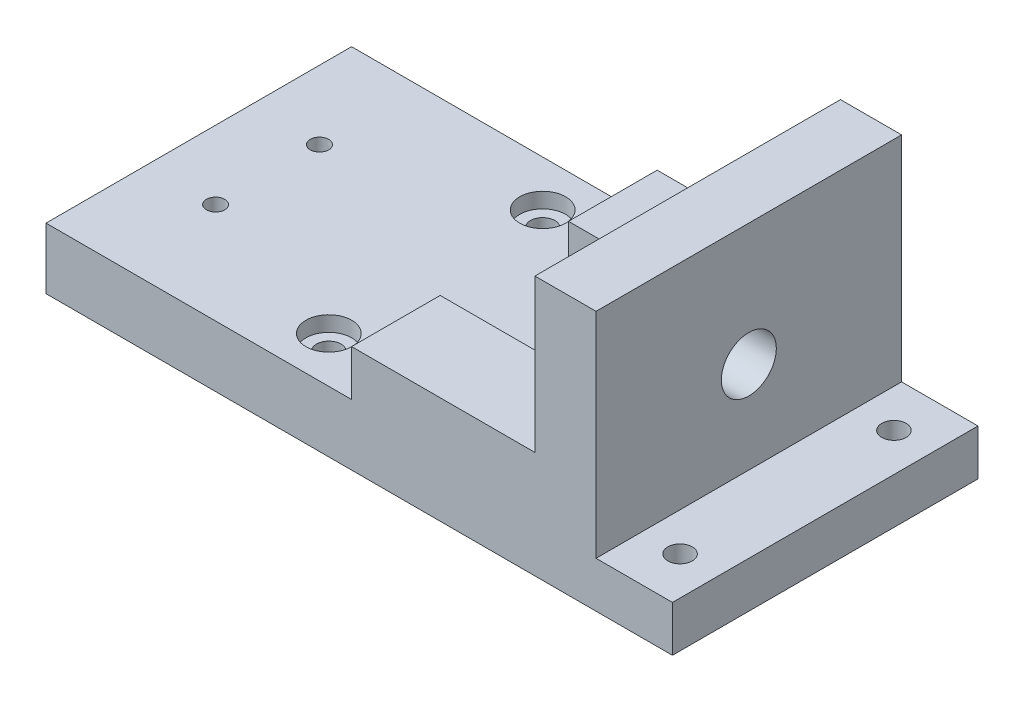
SolidWorks part; units mm, degrees
ref_plane "Front Plane" through (0, 0, 0) normal (0, 0, 1) x (1, 0, 0)
ref_plane "Top Plane" through (0, 0, 0) normal (0, 1, 0) x (1, 0, 0)
ref_plane "Right Plane" through (0, 0, 0) normal (1, 0, 0) x (0, 0, -1)
sketch "Sketch1" plane through (0, 0, 0) normal (0, 0, 1) x (1, 0, 0)
  line L0 (-307.2696, -26.3557) -> (-102.2696, -26.3557)
  line L1 (-102.2696, -26.3557) -> (-102.2696, -11.3557)
  line L5 (-147.2696, 58.6443) -> (-147.2696, 8.6443)
  line L7 (-307.2696, -6.3557) -> (-307.2696, -26.3557)
  line L8 (-307.2696, -6.3557) -> (-207.2696, -6.3557)
  line L9 (-207.2696, -6.3557) -> (-207.2696, 8.6443)
  line L10 (-207.2696, 8.6443) -> (-147.2696, 8.6443)
  line L11 (-147.2696, 58.6443) -> (-127.2696, 58.6443)
  line L12 (-127.2696, 58.6443) -> (-127.2696, -11.3557)
  line L13 (-127.2696, -11.3557) -> (-102.2696, -11.3557)
  dimension "D1" = 20
  dimension "D2" = 205
  dimension "D3" = 15
  dimension "D4" = 70
  dimension "D5" = 60
  dimension "D6" = 15
  dimension "D7" = 25
  dimension "D8" = 20
extrude "Boss-Extrude1" add sketch "Sketch1" along normal blind 100
sketch "Sketch2" plane through (0, 8.6443, 0) normal (0, 1, 0) x (1, 0, 0)
  line L0 (-207.2696, -29) -> (-147.2696, -29)
  line L1 (-207.2696, -100) -> (-207.2696, 0) construction
  line L2 (-147.2696, -100) -> (-147.2696, 0) construction
  line L3 (-207.2696, -29) -> (-207.2696, -71)
  line L4 (-207.2696, -71) -> (-147.2696, -71)
  line L5 (-147.2696, -100) -> (-147.2696, 0) construction
  line L6 (-147.2696, -71) -> (-147.2696, -29)
  line L9 (-207.2696, -100) -> (-207.2696, 0) construction
  point P14 (-207.2696, -50)
  dimension "D1" = 42
extrude "Cut-Extrude1" cut sketch "Sketch2" against normal blind 15
sketch "Sketch3" plane through (0, -6.3557, 0) normal (0, 1, 0) x (1, 0, 0)
  line L1 (-307.2696, -100) -> (-307.2696, 0) construction
  line L2 (-207.2696, 0) -> (-307.2696, 0) construction
  line L3 (-102.2696, -100) -> (-102.2696, 0) construction
  line L4 (-102.2696, 0) -> (-127.2696, 0) construction
  circle A0 centre (-284.7696, -33) radius 3
  circle A1 centre (-114.7696, -15) radius 4
  dimension "D1" = 6
  dimension "D4" = 8
  dimension "D2" = 22.5
  dimension "D3" = 33
  dimension "D5" = 12.5
  dimension "D6" = 15
extrude "Cut-Extrude2" cut sketch "Sketch3" against normal blind 36
ref_plane "Plane1" through (0, 0, 50) normal (0, 0, 1) x (1, 0, 0)
mirror "Mirror1" about plane through (0, 0, 50) normal (0, 0, 1) of "Cut-Extrude2"
sketch "Sketch5" plane through (-127.2696, 0, 0) normal (1, 0, 0) x (0, 0, -1)
  line L0 (-100, 58.6443) -> (0, 58.6443) construction
  line L4 (-100, -26.3557) -> (0, -26.3557) construction
  circle A0 centre (-50, 18.6443) radius 9
  point P7 (-50, 58.6443)
  dimension "D1" = 18
  dimension "D2" = 45
extrude "Cut-Extrude3" cut sketch "Sketch5" against normal blind 26
sketch "Sketch6" plane through (0, -6.3557, 0) normal (0, 1, 0) x (1, 0, 0)
  line L0 (-207.2696, 0) -> (-307.2696, 0) construction
  circle A0 centre (-229.7251, -15) radius 7.5
  circle A1 centre (-229.7251, -15) radius 4
  dimension "D1" = 15
  dimension "D2" = 8
  dimension "D3" = 15
extrude "Cut-Extrude4" cut sketch "Sketch6" against normal blind 26 contours A1
extrude "Cut-Extrude5" cut sketch "Sketch6<3>" against normal blind 5 contours A0
sketch "Sketch6<3>" plane through (0, -6.3557, 0) normal (0, 1, 0) x (1, 0, 0) same geometry as "Sketch6"
mirror "Mirror2" about plane through (0, 0, 50) normal (0, 0, 1) of "Cut-Extrude5", "Cut-Extrude4"
